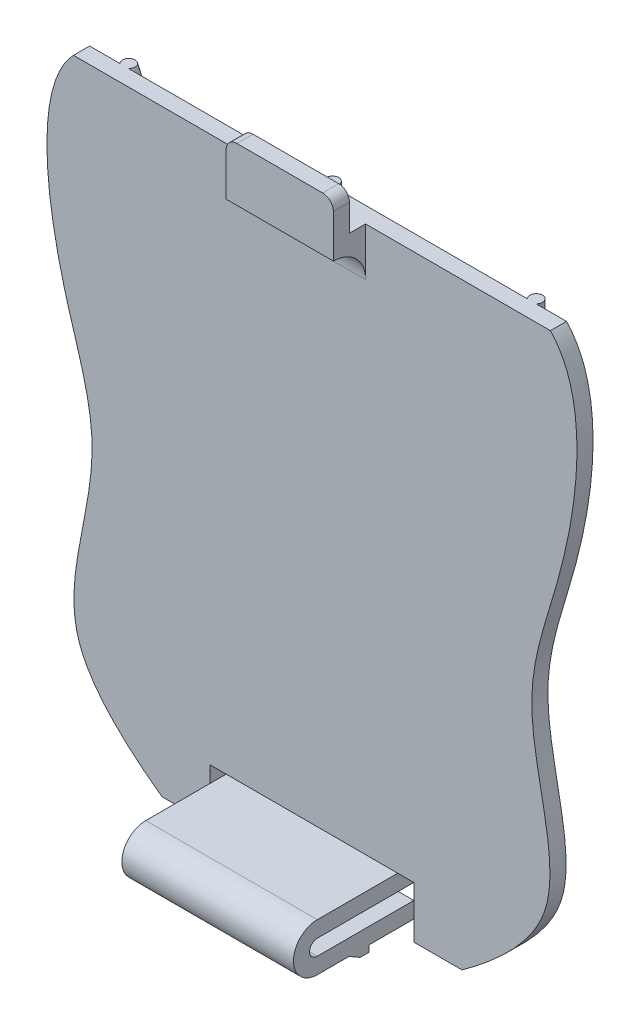
SolidWorks part; units mm, degrees
ref_plane "Front Plane" through (0, 0, 0) normal (0, 0, 1) x (1, 0, 0)
ref_plane "Top Plane" through (0, 0, 0) normal (0, 1, 0) x (1, 0, 0)
ref_plane "Right Plane" through (0, 0, 0) normal (1, 0, 0) x (0, 0, -1)
sketch "Base Sketch" plane through (0, 0, 0) normal (0, 0, 1) x (1, 0, 0)
  line L0 (-21.75, 0) -> (21.75, 0)
  line L1 (21.75, 0) -> (21.75, -20)
  line L2 (21.75, -20) -> (18.5, -20)
  line L3 (18.5, -20) -> (18.5, -50)
  line L4 (18.5, -50) -> (-18.5, -50)
  line L5 (-18.5, -50) -> (-18.5, -20)
  line L6 (-18.5, -20) -> (-21.75, -20)
  line L7 (-21.75, -20) -> (-21.75, 0)
  line L8 (-18.5, -20) -> (18.5, -20) construction
  line L9 (0, 0) -> (0, -33.569) construction
  line L10 (14.39, -57) -> (-14.39, -57)
  spline S0 degree 3 poles (0, 7.677) (-5.9261, 3.8591) (-28.5713, 7.5923) (-25.6422, -17.5275) (-19.7896, -32.1257) (-26.8245, -47.0386) (-17.6574, -54.6681) (-14.39, -57) knots 0 0 0 0 0.278268 0.52501 0.653283 0.848016 1 1 1 1
  spline S1 degree 3 poles (0, 7.677) (5.9261, 3.8591) (28.5713, 7.5923) (25.6422, -17.5275) (19.7896, -32.1257) (26.8245, -47.0386) (17.6574, -54.6681) (14.39, -57) knots 0 0 0 0 0.278268 0.52501 0.653283 0.848016 1 1 1 1
  point P2 (0, 0)
  point P9 (0, -50)
  dimension "D1" = 43.5
  dimension "D2" = 37
  dimension "D3" = 20
  dimension "D4" = 30
  dimension "D5" = 7
sketch "Sketch2" plane through (0, 0, 0) normal (0, 0, 1) x (1, 0, 0)
  line L2 (-13.9874, -55.75) -> (13.9874, -55.75)
  line L3 (-13.9874, -55.75) -> (13.9874, -55.75)
  spline S4 degree 3 poles (1841.0455, -2431.4008) (-190.964, 11.5444) (-24.0265, -92.8903) (18.5264, -51.9348) (19.1135, -51.312) (20.1839, -49.9952) (20.6697, -49.3014) (21.2782, -48.1745) (21.4588, -47.7866) (21.7589, -46.9967) (21.8777, -46.5921) (22.0559, -45.7647) (22.1162, -45.3392) (22.1875, -44.4907) (22.199, -44.0675) (22.1808, -42.8004) (22.0992, -41.9588) (21.8684, -40.2785) (21.7187, -39.4403) (21.2444, -36.9296) (20.8926, -35.259) (20.5771, -32.7335) (20.5072, -31.8884) (20.4922, -30.1866) (20.5522, -29.3294) (20.7306, -28.0354) (20.8045, -27.6029) (20.9744, -26.7454) (21.0704, -26.3191) (21.383, -25.0453) (21.6239, -24.2031) (22.1239, -22.5226) (22.3827, -21.6843) (22.8773, -20.0026) (23.1112, -19.1589) (23.7492, -16.6142) (24.099, -14.9015) (24.4702, -12.2994) (24.568, -11.4265) (24.6957, -9.6662) (24.7256, -8.7779) (24.6911, -7.0117) (24.6278, -6.1307) (24.3615, -4.3749) (24.1617, -3.5156) (23.78, -2.4816) (23.6968, -2.2768) (23.5149, -1.8719) (23.4156, -1.6712) (23.0959, -1.0871) (22.8526, -0.719) (22.2927, -0.0349) (21.971, 0.2821) (21.2792, 0.8335) (20.9085, 1.0736) (20.1303, 1.5012) (19.7246, 1.6873) (18.9064, 2.014) (18.4912, 2.1559) (17.2325, 2.5368) (16.3763, 2.7319) (14.647, 3.0636) (13.774, 3.1994) (12.024, 3.4471) (11.1464, 3.5589) (8.5151, 3.901) (6.762, 4.1344) (4.1752, 4.6819) (3.3201, 4.8978) (-29.47, 15.6306) (-43.2501, 110.066) (538.3214, 2956.4016) knots -2.082102 -2.082102 -2.082102 -2.082102 0.0625 0.0625 0.09375 0.09375 0.125 0.125 0.140625 0.140625 0.15625 0.15625 0.171875 0.171875 0.1875 0.1875 0.21875 0.21875 0.25 0.25 0.3125 0.3125 0.34375 0.34375 0.375 0.375 0.390625 0.390625 0.40625 0.40625 0.4375 0.4375 0.46875 0.46875 0.5 0.5 0.5625 0.5625 0.59375 0.59375 0.625 0.625 0.65625 0.65625 0.6875 0.6875 0.695313 0.695313 0.703125 0.703125 0.71875 0.71875 0.734375 0.734375 0.75 0.75 0.765625 0.765625 0.78125 0.78125 0.8125 0.8125 0.84375 0.84375 0.875 0.875 0.9375 0.9375 0.96875 0.96875 2.154273 2.154273 2.154273 2.154273 only from (13.9874, -55.75) to (0, 6.2243)
  spline S5 degree 3 poles (-594.9628, 2945.6884) (41.4942, 112.322) (29.706, 15.8132) (-3.2503, 4.918) (-4.0893, 4.7031) (-6.6297, 4.1569) (-8.3541, 3.9227) (-11.8071, 3.4722) (-13.5366, 3.263) (-16.1005, 2.7901) (-16.9501, 2.6057) (-18.2085, 2.2461) (-18.6261, 2.1117) (-19.4428, 1.8066) (-19.8429, 1.6358) (-20.6202, 1.2425) (-21.0004, 1.0178) (-21.7078, 0.5084) (-22.0346, 0.2234) (-22.4773, -0.2574) (-22.6179, -0.4272) (-22.8809, -0.7785) (-23.0031, -0.9595) (-23.3448, -1.5164) (-23.5397, -1.9063) (-23.8769, -2.7159) (-24.0168, -3.1302) (-24.2507, -3.9657) (-24.3453, -4.3883) (-24.499, -5.2414) (-24.558, -5.6717) (-24.647, -6.5388) (-24.6767, -6.975) (-24.7286, -8.2752) (-24.7149, -9.1372) (-24.6194, -10.8542) (-24.5373, -11.7093) (-24.2106, -14.2663) (-23.8874, -15.9602) (-23.2855, -18.4899) (-23.0642, -19.3317) (-22.5849, -21.013) (-22.3285, -21.8525) (-21.5683, -24.3717) (-21.0761, -26.0521) (-20.637, -28.5924) (-20.5402, -29.4425) (-20.479, -31.1513) (-20.5182, -32.0104) (-20.7736, -34.5965) (-21.1247, -36.3325) (-21.6251, -38.9349) (-21.7877, -39.802) (-22.0494, -41.5322) (-22.1492, -42.3961) (-22.2161, -44.1249) (-22.1843, -44.9894) (-21.9921, -46.07) (-21.9456, -46.2868) (-21.8372, -46.7114) (-21.7751, -46.9203) (-21.5645, -47.5362) (-21.3928, -47.9332) (-20.8036, -49.0916) (-20.3079, -49.8256) (-19.2266, -51.1866) (-18.637, -51.8213) (-17.3939, -53.031) (-16.7388, -53.6063) (30.2137, -91.9985) (165.553, -15.0321) (-1707.9787, -2527.6218) knots -1.185394 -1.185394 -1.185394 -1.185394 0.03125 0.03125 0.0625 0.0625 0.125 0.125 0.1875 0.1875 0.21875 0.21875 0.234375 0.234375 0.25 0.25 0.265625 0.265625 0.28125 0.28125 0.289062 0.289062 0.296875 0.296875 0.3125 0.3125 0.328125 0.328125 0.34375 0.34375 0.359375 0.359375 0.375 0.375 0.40625 0.40625 0.4375 0.4375 0.5 0.5 0.53125 0.53125 0.5625 0.5625 0.625 0.625 0.65625 0.65625 0.6875 0.6875 0.75 0.75 0.78125 0.78125 0.8125 0.8125 0.84375 0.84375 0.851562 0.851562 0.859375 0.859375 0.875 0.875 0.90625 0.90625 0.9375 0.9375 0.96875 0.96875 3.110392 3.110392 3.110392 3.110392 only from (0, 6.2243) to (-13.9874, -55.75)
  spline S6 degree 3 poles (13.9874, -55.75) (15.3645, -54.7529) (16.693, -53.6995) (18.5264, -51.9348) (19.1135, -51.312) (20.1839, -49.9952) (20.6697, -49.3014) (21.2782, -48.1745) (21.4588, -47.7866) (21.7589, -46.9967) (21.8777, -46.5921) (22.0559, -45.7647) (22.1162, -45.3392) (22.1875, -44.4907) (22.199, -44.0675) (22.1808, -42.8004) (22.0992, -41.9588) (21.8684, -40.2785) (21.7187, -39.4403) (21.2444, -36.9296) (20.8926, -35.259) (20.5771, -32.7335) (20.5072, -31.8884) (20.4922, -30.1866) (20.5522, -29.3294) (20.7306, -28.0354) (20.8045, -27.6029) (20.9744, -26.7454) (21.0704, -26.3191) (21.383, -25.0453) (21.6239, -24.2031) (22.1239, -22.5226) (22.3827, -21.6843) (22.8773, -20.0026) (23.1112, -19.1589) (23.7492, -16.6142) (24.099, -14.9015) (24.4702, -12.2994) (24.568, -11.4265) (24.6957, -9.6662) (24.7256, -8.7779) (24.6911, -7.0117) (24.6278, -6.1307) (24.3615, -4.3749) (24.1617, -3.5156) (23.78, -2.4816) (23.6968, -2.2768) (23.5149, -1.8719) (23.4156, -1.6712) (23.0959, -1.0871) (22.8526, -0.719) (22.2927, -0.0349) (21.971, 0.2821) (21.2792, 0.8335) (20.9085, 1.0736) (20.1303, 1.5012) (19.7246, 1.6873) (18.9064, 2.014) (18.4912, 2.1559) (17.2325, 2.5368) (16.3763, 2.7319) (14.647, 3.0636) (13.774, 3.1994) (12.024, 3.4471) (11.1464, 3.5589) (8.5151, 3.901) (6.762, 4.1344) (4.1752, 4.6819) (3.3201, 4.8978) (1.6358, 5.4491) (0.8063, 5.7831) (0, 6.2243) knots 0 0 0 0 0.0625 0.0625 0.09375 0.09375 0.125 0.125 0.140625 0.140625 0.15625 0.15625 0.171875 0.171875 0.1875 0.1875 0.21875 0.21875 0.25 0.25 0.3125 0.3125 0.34375 0.34375 0.375 0.375 0.390625 0.390625 0.40625 0.40625 0.4375 0.4375 0.46875 0.46875 0.5 0.5 0.5625 0.5625 0.59375 0.59375 0.625 0.625 0.65625 0.65625 0.6875 0.6875 0.695313 0.695313 0.703125 0.703125 0.71875 0.71875 0.734375 0.734375 0.75 0.75 0.765625 0.765625 0.78125 0.78125 0.8125 0.8125 0.84375 0.84375 0.875 0.875 0.9375 0.9375 0.96875 0.96875 1 1 1 1
  spline S7 degree 3 poles (0, 6.2243) (-0.7878, 5.7932) (-1.5997, 5.4637) (-3.2503, 4.918) (-4.0893, 4.7031) (-6.6297, 4.1569) (-8.3541, 3.9227) (-11.8071, 3.4722) (-13.5366, 3.263) (-16.1005, 2.7901) (-16.9501, 2.6057) (-18.2085, 2.2461) (-18.6261, 2.1117) (-19.4428, 1.8066) (-19.8429, 1.6358) (-20.6202, 1.2425) (-21.0004, 1.0178) (-21.7078, 0.5084) (-22.0346, 0.2234) (-22.4773, -0.2574) (-22.6179, -0.4272) (-22.8809, -0.7785) (-23.0031, -0.9595) (-23.3448, -1.5164) (-23.5397, -1.9063) (-23.8769, -2.7159) (-24.0168, -3.1302) (-24.2507, -3.9657) (-24.3453, -4.3883) (-24.499, -5.2414) (-24.558, -5.6717) (-24.647, -6.5388) (-24.6767, -6.975) (-24.7286, -8.2752) (-24.7149, -9.1372) (-24.6194, -10.8542) (-24.5373, -11.7093) (-24.2106, -14.2663) (-23.8874, -15.9602) (-23.2855, -18.4899) (-23.0642, -19.3317) (-22.5849, -21.013) (-22.3285, -21.8525) (-21.5683, -24.3717) (-21.0761, -26.0521) (-20.637, -28.5924) (-20.5402, -29.4425) (-20.479, -31.1513) (-20.5182, -32.0104) (-20.7736, -34.5965) (-21.1247, -36.3325) (-21.6251, -38.9349) (-21.7877, -39.802) (-22.0494, -41.5322) (-22.1492, -42.3961) (-22.2161, -44.1249) (-22.1843, -44.9894) (-21.9921, -46.07) (-21.9456, -46.2868) (-21.8372, -46.7114) (-21.7751, -46.9203) (-21.5645, -47.5362) (-21.3928, -47.9332) (-20.8036, -49.0916) (-20.3079, -49.8256) (-19.2266, -51.1866) (-18.637, -51.8213) (-17.3939, -53.031) (-16.7388, -53.6063) (-15.3883, -54.7106) (-14.6941, -55.2383) (-13.9874, -55.75) knots 0 0 0 0 0.03125 0.03125 0.0625 0.0625 0.125 0.125 0.1875 0.1875 0.21875 0.21875 0.234375 0.234375 0.25 0.25 0.265625 0.265625 0.28125 0.28125 0.289062 0.289062 0.296875 0.296875 0.3125 0.3125 0.328125 0.328125 0.34375 0.34375 0.359375 0.359375 0.375 0.375 0.40625 0.40625 0.4375 0.4375 0.5 0.5 0.53125 0.53125 0.5625 0.5625 0.625 0.625 0.65625 0.65625 0.6875 0.6875 0.75 0.75 0.78125 0.78125 0.8125 0.8125 0.84375 0.84375 0.851562 0.851562 0.859375 0.859375 0.875 0.875 0.90625 0.90625 0.9375 0.9375 0.96875 0.96875 1 1 1 1
  dimension "D1" = 1.25
extrude "Low Plate" add sketch "Sketch2" along normal blind 1.5
sketch "Sketch3" plane through (0, 0, 1.5) normal (0, 0, 1) x (1, 0, 0)
  line L0 (-13.9874, -55.75) -> (13.9874, -55.75) construction
  line L1 (-9.5, -55.75) -> (9.5, -55.75)
  line L2 (-9.5, -55.75) -> (-9.5, -50.933)
  line L3 (-9.5, -50.933) -> (9.5, -50.933)
  line L4 (9.5, -55.75) -> (9.5, -50.933)
  line L5 (0, 0) -> (0, -33.569) construction
  line L6 (18.5, -50) -> (-18.5, -50) construction
  point P6 (0, -50.933)
  dimension "D1" = 19
  dimension "D2" = 0.933
extrude "Cut-Extrude1" cut sketch "Sketch3" against normal through all
sketch "Sketch5" plane through (0, 0, 0) normal (1, 0, 0) x (0, 0, -1)
  line L1 (0, -50.933) -> (-9, -50.933)
  line L2 (0, -50.933) -> (0, -52.433)
  line L3 (0, -52.433) -> (-9, -52.433)
  line L4 (-9, -50.933) -> (-9, -52.433)
  line L5 (0, -55.383) -> (-9, -55.383)
  line L6 (0, -55.383) -> (0, -53.883)
  line L7 (0, -53.883) -> (-9, -53.883)
  line L8 (-9, -55.383) -> (-9, -53.883)
  arc A0 (-9, -50.933) -> (-9, -55.383) centre (-9, -53.158) ccw
  arc A1 (-9, -52.433) -> (-9, -53.883) centre (-9, -53.158) ccw
  dimension "D1" = 1.5
  dimension "D2" = 1.5
  dimension "D3" = 9
  dimension "D4" = 4.45
extrude "Tongue" add sketch "Sketch5" along normal mid plane 16 contours L1 L4 L3 L2 | A1 L4 A0 L8 | L8 L5 L6 L7 region at (0, -51.683, 4.5) region at (0, -53.158, 10.0199) region at (0, -54.633, 4.5)
sketch "Sketch6" plane through (0, -55.383, 0) normal (0, -1, 0) x (1, 0, 0)
  line L0 (0, 0) -> (-25.9632, 0) construction
  line L1 (-5, 0) -> (5, 0)
  line L2 (-5, 0) -> (-5, 3.5)
  line L3 (-2, 6.5) -> (2, 6.5)
  line L4 (5, 0) -> (5, 3.5)
  arc A0 (2, 6.5) -> (5, 3.5) centre (2, 3.5) cw
  arc A1 (-5, 3.5) -> (-2, 6.5) centre (-2, 3.5) cw
  point P6 (0, 0)
  dimension "D3" = 3
  dimension "D1" = 10
  dimension "D2" = 6.5
extrude "Tongue Button" add sketch "Sketch6" along normal blind 1.5
sketch "Sketch7" plane through (0, 0, 0) normal (1, 0, 0) x (0, 0, -1)
  line L1 (0, -1.5) -> (-4.5, -1.5)
  line L2 (0, -1.5) -> (0, 0)
  line L3 (0, 0) -> (-4.5, 0)
  line L4 (-4.5, -1.5) -> (-4.5, 0)
  line L5 (-4.5, 0) -> (-3, 0)
  line L6 (-4.5, 0) -> (-4.5, 3.5)
  line L7 (-4.5, 3.5) -> (-3, 3.5)
  line L8 (-3, 0) -> (-3, 3.5)
  dimension "D1" = 1.5
  dimension "D2" = 5
  dimension "D3" = 1.5
  dimension "D4" = 4.5
extrude "Boss-Extrude4" add sketch "Sketch7" along normal mid plane 10 contours L4 L1 L2 L3 | L3 L8 L7 L6 region at (0, -0.75, 2.25) region at (0, 1.75, 3.75)
sketch "Sketch8" plane through (0, 0, 0) normal (1, 0, 0) x (0, 0, -1)
  line L1 (-3, 0) -> (0, 0)
  line L2 (-3, 0) -> (-3, 6.2243)
  line L3 (-3, 6.2243) -> (0, 6.2243)
  line L4 (0, 0) -> (0, 6.2243)
extrude "Cut-Extrude2" cut sketch "Sketch8" against normal mid plane 60
fillet "Fillet 3mm" radius 3 1 edges at (0, -1.5, 1.5)
fillet "Fillet2" radius 1 2 edges at (-5, 3.5, 3.75) (5, 3.5, 3.75)
sketch "Sketch9" plane through (-8, 0, 0) normal (-1, 0, 0) x (0, 0, 1)
  line L0 (6.0392, -55.383) -> (5, -55.983)
  line L1 (0, -55.383) -> (9, -55.383) construction
  line L2 (5, -55.983) -> (5, -55.383)
  line L3 (3.5, -55.383) -> (6.5, -55.383) construction
  line L4 (5, -55.383) -> (6.0392, -55.383)
  line L5 (1.5, -55.75) -> (1.5, 0) construction
  line L7 (5, -55.983) -> (4.2, -55.983)
  line L8 (5, -55.983) -> (5, -55.383)
  line L9 (5, -55.383) -> (4.2, -55.383)
  line L10 (4.2, -55.983) -> (4.2, -55.383)
  line M7 (0, -55.383) -> (9, -55.383)
  dimension "D1" = 3.5
  dimension "D2" = 30
  dimension "D3" = 0.8
  dimension "D4" = 0.6
extrude "Right Clips" add sketch "Sketch9" against normal blind 2 contours L2 L0 M7 | L10 L7 L2 M7 region at (-8, -55.583, 5.3464) region at (-8, -55.683, 4.6)
mirror "Left Clips" about plane through (0, 0, 0) normal (1, 0, 0) of "Right Clips"
sketch "Sketch10" plane through (0, 0, 0) normal (1, 0, 0) x (0, 0, -1)
  line L0 (0, -56.883) -> (-3.5, -56.883) construction
  line L1 (-0.6, -56.883) -> (0, -56.883)
  line L2 (-1.4, -56.883) -> (-0.8, -56.883)
  line L3 (-2.2, -56.883) -> (-1.6, -56.883)
  line L4 (-3, -56.883) -> (-2.4, -56.883)
  line L5 (-3.8, -56.883) -> (-3.2, -56.883)
  line L6 (-4.6, -56.883) -> (-4, -56.883)
  arc A0 (0, -56.883) -> (-0.6, -56.883) centre (-0.3, -56.883) cw
  arc A1 (-0.8, -56.883) -> (-1.4, -56.883) centre (-1.1, -56.883) cw
  arc A2 (-1.6, -56.883) -> (-2.2, -56.883) centre (-1.9, -56.883) cw
  arc A3 (-2.4, -56.883) -> (-3, -56.883) centre (-2.7, -56.883) cw
  arc A4 (-3.2, -56.883) -> (-3.8, -56.883) centre (-3.5, -56.883) cw
  arc A5 (-4, -56.883) -> (-4.6, -56.883) centre (-4.3, -56.883) cw
  dimension "D1" = 0.3
  dimension "D2" = 6
extrude "Clips Ribbs" add sketch "Sketch10" along normal mid plane 9
sketch "Sketch11" plane through (0, 0, 0) normal (0, 1, 0) x (1, 0, 0)
  line L0 (-22.2383, 0) -> (22.2377, 0) construction
  line L1 (-19.4, 0) -> (-18.6, 0)
  line L2 (-0.4, 0) -> (0.4, 0)
  line L3 (18.6, 0) -> (19.4, 0)
  arc A0 (-19.4, 0) -> (-18.6, 0) centre (-19, 0.42) cw
  arc A1 (-0.4, 0) -> (0.4, 0) centre (0, 0.42) cw
  arc A2 (18.6, 0) -> (19.4, 0) centre (19, 0.42) cw
  point P11 (0, 0)
  dimension "D1" = 1
  dimension "D2" = 0.8
  dimension "D3" = 19
  dimension "D4" = 19
extrude "Boss-Extrude7" add sketch "Sketch11" against normal blind 47
sketch "Sketch12" plane through (0, 0, 0) normal (0, 0, -1) x (-1, 0, 0)
  line L0 (-19, 0) -> (0.58, -42.3204)
  line L1 (-18.42, 0) -> (-19.58, 0) construction
  line L2 (0.58, -47) -> (0.58, 0) construction
extrude "Boss-Extrude8" add sketch "Sketch11<2>" along direction (-0.4199, -0.9076, 0) on the side against the normal blind 45 contours A2 L3
sketch "Sketch11<2>" plane through (0, 0, 0) normal (0, 1, 0) x (1, 0, 0) same geometry as "Sketch11"
mirror "Mirror2" about plane through (0, 0, 0) normal (1, 0, 0) of "Boss-Extrude8"
